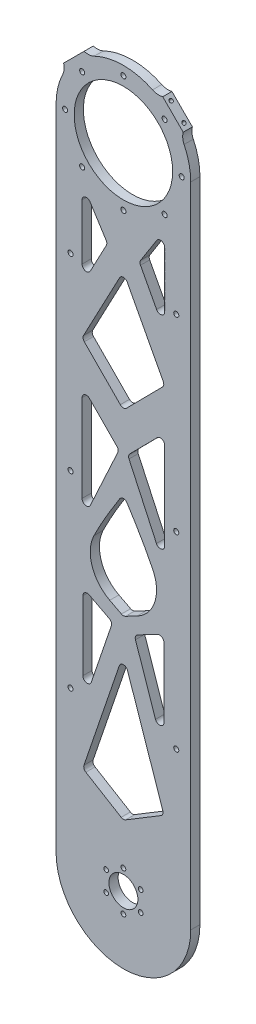
SolidWorks part; units mm, degrees
material "6061-T6 (SS)"
ref_plane "Front Plane" through (0, 0, 0) normal (0, 0, 1) x (1, 0, 0)
ref_plane "Top Plane" through (0, 0, 0) normal (0, 1, 0) x (1, 0, 0)
ref_plane "Right Plane" through (0, 0, 0) normal (1, 0, 0) x (0, 0, -1)
sketch "Sketch2" plane through (0, 0, 0) normal (0, 0, 1) x (1, 0, 0)
  line L0 (0, 0) -> (0, 500) construction
  line L1 (-46.5, 0) -> (-46.5, 500)
  line L2 (46.5, 0) -> (46.5, 500)
  arc A0 (-46.5, 0) -> (46.5, 0) centre (0, 0) ccw
  arc A1 (46.5, 500) -> (-46.5, 500) centre (0, 500) ccw
  circle A2 centre (0, 500) radius 37.25 construction
  circle A3 centre (0, 0) radius 10
  circle A4 centre (0, 13.75) radius 1.65
  circle A5 centre (0, 0) radius 13.75 construction
  circle A6 centre (11.9078, 6.875) radius 1.65
  circle A7 centre (11.9078, -6.875) radius 1.65
  circle A8 centre (0, -13.75) radius 1.65
  circle A9 centre (-11.9078, -6.875) radius 1.65
  circle A10 centre (-11.9078, 6.875) radius 1.65
  point P3 (0, 250)
  point P27 (0, 0)
  dimension "D2" = 74.5
  dimension "D4" = 20
  dimension "D5" = 3.3
  dimension "D6" = 27.5
  dimension "D3" = 46.5
  dimension "D1" = 500
  dimension "D7" = 6
extrude "Boss-Extrude1" add sketch "Sketch2" along normal blind 6.35
sketch "Sketch4" plane through (0, 0, 6.35) normal (0, 0, 1) x (1, 0, 0)
  line L0 (0, 500) -> (0, 999.1647) construction
  line L29 (46.5, 500) -> (-46.5, 500) construction
  line L31 (28.0053, 59.376) -> (0, 42.4117)
  line L32 (0, 141.6934) -> (28.0053, 59.376)
  line L33 (-28.0053, 59.376) -> (0, 141.6934)
  line L34 (0, 42.4117) -> (-28.0053, 59.376)
  line L35 (-7.5, 156.9059) -> (-28.0053, 96.6336)
  line L36 (-28.0053, 167.5829) -> (-7.5, 156.9059)
  line L37 (-28.0053, 96.6336) -> (-28.0053, 167.5829)
  line L38 (28.0053, 167.5829) -> (7.5, 156.9059)
  line L39 (28.0053, 96.6336) -> (28.0053, 167.5829)
  line L40 (7.5, 156.9059) -> (28.0053, 96.6336)
  line L41 (0, 164.2751) -> (28.5505, 179.1412)
  line L42 (0, 164.2751) -> (-28.5505, 179.1412)
  line L43 (28.5505, 259.5868) -> (3, 314.9383)
  line L44 (28.5505, 340.7931) -> (28.5505, 259.5868)
  line L45 (3, 314.9383) -> (28.5505, 340.7931)
  line L46 (-3, 314.9383) -> (-28.5505, 340.7931)
  line L47 (-28.5505, 259.5868) -> (-3, 314.9383)
  line L48 (-28.5505, 340.7931) -> (-28.5505, 259.5868)
  line L49 (0, 423.1428) -> (-28.5505, 369.2462)
  line L50 (-28.5505, 369.2462) -> (0, 340.3557)
  line L51 (0, 340.3557) -> (28.5505, 369.2462)
  line L52 (0, 423.1428) -> (28.5505, 369.2462)
  line L53 (-28.5505, 462.0952) -> (-28.5505, 401.2902)
  line L54 (-11, 434.4215) -> (-28.5505, 462.0952)
  line L55 (-28.5505, 401.2902) -> (-11, 434.4215)
  line L56 (28.5505, 401.2902) -> (11, 434.4215)
  line L57 (28.5505, 462.0952) -> (28.5505, 401.2902)
  line L58 (11, 434.4215) -> (28.5505, 462.0952)
  arc A0 (46.5, 500) -> (-46.5, 500) centre (0, 500) ccw construction
  arc A1 (46.5, 500) -> (-46.5, 500) centre (0, 500) ccw construction
  spline S2 degree 3 poles (28.5505, 179.1412) (45.3203, 216.9857) (19.4301, 259.7903) (0, 290.0258) knots 0 0 0 0 1 1 1 1
  spline S3 degree 3 poles (-28.5505, 179.1412) (-45.3203, 216.9857) (-19.4301, 259.7903) (0, 290.0258) knots 0 0 0 0 1 1 1 1
extrude "Cut-Extrude1" cut sketch "Sketch4" against normal blind 10
fillet "Fillet3" radius 3 30 edges at (-11, 434.4215, 3.175) (-28.5505, 401.2902, 3.175) (28.5505, 401.2902, 3.175) (11, 434.4215, 3.175) (28.5505, 462.0952, 3.175) (-28.5505, 462.0952, 3.175) (0, 423.1428, 3.175) (-28.5505, 369.2462, 3.175) (28.5505, 369.2462, 3.175) (0, 340.3557, 3.175) (28.5505, 340.7931, 3.175) (-28.5505, 340.7931, 3.175) (-3, 314.9383, 3.175) (3, 314.9383, 3.175) (28.5505, 259.5868, 3.175) (-28.5505, 259.5868, 3.175) (28.5505, 179.1412, 3.175) (0, 290.0258, 3.175) (-28.5505, 179.1412, 3.175) (0, 164.2751, 3.175) (-28.0053, 96.6336, 3.175) (28.0053, 96.6336, 3.175) (7.5, 156.9059, 3.175) (-28.0053, 167.5829, 3.175) (28.0053, 167.5829, 3.175) (0, 141.6934, 3.175) (28.0053, 59.376, 3.175) (-28.0053, 59.376, 3.175) (0, 42.4117, 3.175) (-7.5, 156.9059, 3.175)
sketch "Sketch5" plane through (0, 0, 6.35) normal (0, 0, 1) x (1, 0, 0)
  line L0 (0, -46.5) -> (108.8395, -46.5) construction
  line L1 (46.5, 100) -> (-46.5, 100) construction
  line L2 (46.5, 0) -> (46.5, 500) construction
  line L3 (-46.5, 500) -> (-46.5, 0) construction
  line L4 (-46.5, 106.35) -> (46.5, 106.35) construction
  line L5 (36.5, 106.35) -> (36.5, 100) construction
  line L6 (0, 106.35) -> (0, 100) construction
  line L7 (-46.5, 256.35) -> (46.5, 256.35) construction
  line L8 (-46.5, 181.35) -> (46.5, 181.35) construction
  line L9 (-46.5, 337.7) -> (46.5, 337.7) construction
  arc A1 (-46.5, 0) -> (46.5, 0) centre (0, 0) ccw construction
  circle A2 centre (36.5, 103.175) radius 1.75
  circle A3 centre (-36.5, 103.175) radius 1.75
  circle A4 centre (36.5, 259.525) radius 1.75
  circle A5 centre (-36.5, 259.525) radius 1.75
  circle A6 centre (36.5, 415.875) radius 1.75
  circle A7 centre (-36.5, 415.875) radius 1.75
  point P18 (36.5, 103.175)
  dimension "D2" = 3.5
  dimension "D1" = 146.5
  dimension "D3" = 10
  dimension "D4" = 6.35
  dimension "D5" = 150
  dimension "D6" = 81.35
  dimension "D7" = 81.35
extrude "Cut-Extrude2" cut sketch "Sketch5" against normal through all
sketch "Sketch6" plane through (0, 0, 6.35) normal (0, 0, 1) x (1, 0, 0)
  circle A0 centre (0, 500) radius 26.5
  arc A1 (46.5, 500) -> (-46.5, 500) centre (0, 500) ccw construction
  arc A2 (46.5, 500) -> (-46.5, 500) centre (0, 500) ccw construction
  dimension "D1" = 20
extrude "Cut-Extrude3" cut sketch "Sketch6" against normal blind 10
sketch "Sketch7" plane through (0, 0, 6.35) normal (0, 0, 1) x (1, 0, 0)
  line L1 (40.0163, 523.6842) -> (44.1104, 529.9682) construction
  line L2 (23.6842, 540.0163) -> (29.9682, 544.1104) construction
  line L3 (44.1104, 529.9682) -> (29.9682, 544.1104)
  line L4 (0, 500) -> (37.0393, 537.0393) construction
  line L5 (0, 500) -> (0, 546.5) construction
  arc A0 (46.5, 500) -> (-46.5, 500) centre (0, 500) ccw construction
  arc A1 (29.9682, 544.1104) -> (16.4747, 543.4837) centre (22.4977, 559.381) cw
  arc A2 (44.1104, 529.9682) -> (43.4837, 516.4747) centre (59.381, 522.4977) ccw
  arc A3 (16.4747, 543.4837) -> (43.4837, 516.4747) centre (0, 500) cw
  dimension "D3" = 17
  dimension "D5" = 17
  dimension "D1" = 20
  dimension "D2" = 7.5
  dimension "D4" = 8
  dimension "D6" = 8
  dimension "D7" = 45
extrude "Boss-Extrude2" add sketch "Sketch7" against normal up to surface (6.35 mm away) up to face at (26.5, 500, 0)
sketch "Sketch8" plane through (287.0393, 287.0393, 0) normal (0.7071, 0.7071, 0) x (0, 0, -1)
  line L0 (0, 363.5534) -> (-6.35, 363.5534) construction
  line L1 (0, 343.5534) -> (-6.35, 343.5534) construction
  line L2 (-6.35, 343.5534) -> (-6.35, 363.5534) construction
  point P0 (-3.175, 359.5534)
  point P1 (-3.175, 347.5534)
  dimension "D1" = 4
  dimension "D2" = 4
  dimension "D3" = 3.175
hole_wizard "Tap Drill for M3x0.5 Tap1" positions "Sketch8" profile "Sketch9" hole size "M3x0.5" standard "ANSI Metric"
sketch "Sketch9" plane through (32.7967, 541.282, 3.175) normal (0, 0, 1) x (-0.7071, 0.7071, 0)
  line L0 (0, 0) -> (0, 5.7511)
  line L1 (0, 5.7511) -> (1.25, 5)
  line L2 (1.25, 5) -> (1.25, 0)
  line L5 (1.25, 0) -> (0, 0)
  line L10 (0, 5.7511) -> (-1.25, 5) construction
  line L11 (0, -6.35) -> (0, 107.95) construction
  dimension "Hole Dia." = 2.5
  dimension "Hole Depth" = 5
  dimension "Drill Angle" = 118
pattern_circular "CirPattern2" count 2 every 90 about axis through (0, 500, -3.65) along (0, 0, 1) of "Boss-Extrude2", "Tap Drill for M3x0.5 Tap1"
sketch "Sketch10" plane through (0, 0, 6.35) normal (0, 0, 1) x (1, 0, 0)
  line L0 (-43.4837, 516.4747) -> (-63.4837, 516.4747)
  line L1 (43.4837, 516.4747) -> (63.4837, 516.4747)
  arc A0 (43.4837, 516.4747) -> (-43.4837, 516.4747) centre (0, 500) ccw
  arc A1 (46.5, 500) -> (43.4837, 516.4747) centre (0, 500) ccw construction
  arc A2 (-63.4837, 516.4747) -> (63.4837, 516.4747) centre (0, 500) cw
  dimension "D1" = 19.0866
  dimension "D2" = 20
extrude "Cut-Extrude4" cut sketch "Sketch10" against normal through all
sketch "Sketch11" plane through (0, 0, 6.35) normal (0, 0, 1) x (1, 0, 0)
  circle A0 centre (0, 500) radius 34
  circle A1 centre (0, 500) radius 26.5 construction
  dimension "D1" = 68
extrude "Cut-Extrude5" cut sketch "Sketch11" against normal through all
sketch "Sketch12" plane through (0, 0, 6.35) normal (0, 0, 1) x (1, 0, 0)
  line L0 (0, 534) -> (0, 546.5) construction
  circle A0 centre (0, 500) radius 40.25 construction
  circle A1 centre (0, 500) radius 34 construction
  circle A3 centre (0, 540.25) radius 1.75
  circle A4 centre (28.461, 528.461) radius 1.75
  circle A5 centre (40.25, 500) radius 1.75
  circle A6 centre (28.461, 471.539) radius 1.75
  circle A7 centre (0, 459.75) radius 1.75
  circle A8 centre (-28.461, 471.539) radius 1.75
  circle A9 centre (-40.25, 500) radius 1.75
  circle A10 centre (-28.461, 528.461) radius 1.75
  arc A11 (46.5, 500) -> (-46.5, 500) centre (0, 500) ccw construction
  point P4 (0, 540.25)
  point P36 (0, 500)
  dimension "D1" = 3.5
  dimension "D2" = 8
extrude "Cut-Extrude6" cut sketch "Sketch12" against normal through all both and the other way through all
sketch "Sketch13" plane through (0, 0, 0) normal (0, 0, -1) x (-1, 0, 0)
  line L0 (28.984, 180.1429) -> (28.984, 234.0954) construction
  line L1 (-28.984, 180.1429) -> (-28.984, 234.0954) construction
  line L2 (46.5, 234.0954) -> (-46.5, 234.0954)
  line L3 (46.5, 500) -> (46.5, 0) construction
  line L4 (-46.5, 0) -> (-46.5, 500) construction
  line L5 (46.5, 180.1429) -> (-46.5, 180.1429)
  line L6 (-46.5, 234.0954) -> (-46.5, 180.1429)
  line L7 (46.5, 234.0954) -> (46.5, 180.1429)
  spline S0 degree 3 poles (2.5314, 286.068) (21.3968, 256.4039) (44.1773, 216.1126) (28.984, 180.1429) knots 0.042883 0.042883 0.042883 0.042883 0.991187 0.991187 0.991187 0.991187 construction
  spline S1 degree 3 poles (-28.984, 180.1429) (-44.1773, 216.1126) (-21.3968, 256.4039) (-2.5314, 286.068) knots 0.008813 0.008813 0.008813 0.008813 0.957117 0.957117 0.957117 0.957117 construction
extrude "Cut-Extrude7" cut sketch "Sketch13" against normal through all
move or copy body "Body-Move/Copy1" bodies to move or copy 111 copy no translate (0, -52.7177, 0) parameters "D1"=0, "D2"=52.7177, "D3"=0
sketch "Sketch14" plane through (0, 180.1429, 0) normal (0, 1, 0) x (1, 0, 0)
  line L0 (-28.984, 0) -> (-46.5, 0) construction
  line L1 (-46.5, 0) -> (-46.5, -6.35) construction
  line L2 (-46.5, -6.35) -> (-28.984, -6.35) construction
  line L3 (-28.984, -6.35) -> (-28.984, 0) construction
  line L4 (28.984, -6.35) -> (46.5, -6.35) construction
  line L5 (46.5, -6.35) -> (46.5, 0) construction
  line L6 (46.5, 0) -> (28.984, 0) construction
  line L7 (28.984, 0) -> (28.984, -6.35) construction
  line L8 (-28.984, 0) -> (-46.5, 0)
  line L9 (-46.5, 0) -> (-46.5, -6.35)
  line L10 (-46.5, -6.35) -> (-28.984, -6.35)
  line L11 (-28.984, -6.35) -> (-28.984, 0)
  line L12 (28.984, -6.35) -> (46.5, -6.35)
  line L13 (46.5, -6.35) -> (46.5, 0)
  line L14 (46.5, 0) -> (28.984, 0)
  line L15 (28.984, 0) -> (28.984, -6.35)
extrude "Boss-Extrude3" add sketch "Sketch14" along normal up to surface (1.2348 mm away) up to face at (37.742, 181.3777, 3.175)
sketch "Sketch15" plane through (0, 0, 0) normal (0, 0, -1) x (-1, 0, 0)
  line L0 (-1.3855, 164.9966) -> (-27.606, 178.6494) construction
  line L1 (28.984, 181.3777) -> (28.984, 180.1429)
  line L2 (-28.984, 181.3777) -> (-28.984, 180.1429) construction
  line L3 (-9.4381, 169.1895) -> (-27.606, 178.6494)
  line L4 (-28.984, 181.3777) -> (-28.984, 180.1429)
  line L5 (0, 493.7823) -> (0, -46.5) construction
  line L6 (9.4381, 169.1895) -> (27.606, 178.6494)
  arc A0 (-20.3344, 202.3794) -> (-9.4381, 169.1895) centre (2.1078, 191.3636) ccw
  arc A1 (-28.984, 180.1429) -> (-27.606, 178.6494) centre (-26.2204, 181.3103) ccw construction
  arc A2 (-28.984, 180.1429) -> (-27.606, 178.6494) centre (-26.2204, 181.3103) ccw
  arc A3 (46.5, 447.2823) -> (-46.5, 447.2823) centre (0, 447.2823) ccw construction
  arc A4 (-46.5, 0) -> (46.5, 0) centre (0, 0) ccw construction
  arc A5 (28.984, 180.1429) -> (27.606, 178.6494) centre (26.2204, 181.3103) cw
  arc A6 (20.3344, 202.3794) -> (9.4381, 169.1895) centre (-2.1078, 191.3636) cw
  spline S0 degree 3 poles (1953.7087, 263.1445) (-2215.7642, -533.3919) (2154.4506, 1213.369) (-1849.5555, -532.5784) knots -2.670349 -2.670349 -2.670349 -2.670349 4.338748 4.338748 4.338748 4.338748 only from (-28.984, 181.3777) to (-2.5314, 233.3503) construction
  spline S1 degree 3 poles (28.984, 181.3777) (26.6659, 188.5284) (23.6788, 195.566) (20.3344, 202.3794) knots 0.47109 0.47109 0.47109 0.47109 0.656208 0.656208 0.656208 0.656208
  spline S2 degree 3 poles (-28.984, 181.3777) (-26.6659, 188.5284) (-23.6788, 195.566) (-20.3344, 202.3794) knots 0.47109 0.47109 0.47109 0.47109 0.656208 0.656208 0.656208 0.656208
  dimension "D1" = 25
  dimension "D2" = 540.2823
extrude "Boss-Extrude4" add sketch "Sketch15" against normal up to surface (6.35 mm away) up to face at (2.6453, 187.7844, 6.35)
sketch "Sketch16" plane through (0, 0, 0) normal (0, 0, -1) x (-1, 0, 0)
  line L0 (36.5, 103.175) -> (36.5, 363.1573) construction
  line L1 (-36.5, 103.175) -> (-36.5, 363.1573) construction
  circle A0 centre (-36.5, 363.1573) radius 1.75 construction
  circle A1 centre (36.5, 363.1573) radius 1.75 construction
  circle A2 centre (-36.5, 103.175) radius 1.75 construction
  circle A3 centre (36.5, 103.175) radius 1.75 construction
  circle A4 centre (-36.5, 363.1573) radius 1.75 construction
  circle A5 centre (36.5, 363.1573) radius 1.75 construction
  circle A6 centre (-36.5, 103.175) radius 1.75 construction
  circle A7 centre (36.5, 103.175) radius 1.75 construction
  circle A8 centre (36.5, 233.1662) radius 1.75
  circle A9 centre (-36.5, 233.1662) radius 1.75
  point P16 (36.5, 233.1662)
  point P18 (36.5, 233.1662)
extrude "Cut-Extrude8" cut sketch "Sketch16" against normal through all
sketch "Sketch17" plane through (0, 0, 0) normal (0, 0, -1) x (-1, 0, 0)
  circle A0 centre (36.5, 206.8073) radius 1.75 construction
  circle A1 centre (-36.5, 206.8073) radius 1.75 construction
  circle A2 centre (36.5, 206.8073) radius 1.75
  circle A3 centre (-36.5, 206.8073) radius 1.75
extrude "Boss-Extrude5" add sketch "Sketch17" against normal up to surface (6.35 mm away) up to face at (-34.75, 233.1662, 6.35)
sketch "Sketch18" plane through (0, 0, 0) normal (0, 0, -1) x (-1, 0, 0)
  line L0 (0, 447.2823) -> (0, 493.7823) construction
  line L1 (0, 447.2823) -> (32.8805, 480.1628) construction
  line L2 (-10, 492.6943) -> (-10, 495.6943) construction
  line L3 (25.0401, 486.4645) -> (27.1614, 488.5858)
  line L4 (27.1614, 488.5858) -> (41.3035, 474.4437)
  line L5 (41.3035, 474.4437) -> (39.1822, 472.3224)
  line L6 (25.0401, 486.4645) -> (39.1822, 472.3224)
  line L7 (-10, 495.6943) -> (10, 495.6943) construction
  line L8 (10, 495.6943) -> (10, 492.6943) construction
  line L9 (-10, 492.6943) -> (10, 492.6943) construction
  line L10 (-39.1822, 472.3224) -> (-41.3035, 474.4437)
  line L11 (-41.3035, 474.4437) -> (-27.1614, 488.5858)
  line L12 (-27.1614, 488.5858) -> (-25.0401, 486.4645)
  line L13 (-39.1822, 472.3224) -> (-25.0401, 486.4645)
  arc A0 (46.5, 447.2823) -> (-46.5, 447.2823) centre (0, 447.2823) ccw construction
  point P11 (32.1111, 479.3934)
  point P13 (0, 492.6943)
  dimension "D1" = 45
  dimension "D2" = 20
  dimension "D3" = 3
  dimension "D4" = 3
extrude "Boss-Extrude6" add sketch "Sketch18" against normal up to surface (6.35 mm away) up to face at (-34.75, 233.1662, 6.35)
sketch "Sketch20" plane through (-257.8736, 257.8736, 0) normal (-0.7071, 0.7071, 0) x (0, 0, 1)
  line L0 (6.35, 316.2764) -> (0, 316.2764) construction
  line L1 (6.35, 306.2764) -> (6.35, 326.2764) construction
  line L2 (0, 306.2764) -> (0, 326.2764) construction
  point P0 (3.175, 322.5264)
  point P9 (3.175, 316.2764)
  point P10 (3.175, 310.0264)
  dimension "D1" = 12.5
hole_wizard "M3x0.5 Tapped Hole1" positions "Sketch20" profile "Sketch21" tap size "M3x0.5" standard "ANSI Metric"
sketch "Sketch21" plane through (-29.813, 485.9342, 3.175) normal (0, 0, 1) x (-0.7071, -0.7071, 0)
  line L0 (0, 0) -> (0, 8.2511)
  line L1 (0, 8.2511) -> (1.25, 7.5)
  line L2 (1.25, 7.5) -> (1.25, 0)
  line L5 (1.25, 0) -> (0, 0)
  line L10 (0, 8.2511) -> (-1.25, 7.5) construction
  line L11 (0, -6.35) -> (0, 107.95) construction
  dimension "Tap Drill Dia." = 2.5
  dimension "Tap Drill Depth" = 7.5
  dimension "Drill Angle" = 118
cosmetic thread "Hole Thread1" parameters "D1"=6, "D2"=3
cosmetic thread "Hole Thread2" parameters "D1"=6, "D2"=3
pattern_circular "CirPattern3" count 2 over 90 about axis through (0, 447.2823, 0) along (0, 0, 1) of "M3x0.5 Tapped Hole1" reverse direction yes
cosmetic thread "Hole Thread5" parameters "D1"=6, "D2"=3
cosmetic thread "Hole Thread6" parameters "D1"=6, "D2"=3
cosmetic thread "Hole Thread7" parameters "D1"=6, "D2"=3
cosmetic thread "Hole Thread8" parameters "D1"=6, "D2"=3
fillet "Fillet4" radius 10 4 edges at (-39.1822, 472.3224, 3.175) (-25.0401, 486.4645, 3.175) (39.1822, 472.3224, 3.175) (25.0401, 486.4645, 3.175)
equation "\"L1L\"=500"
equation "\"L1Thick\"=6.35"
equation "\"D1@Sketch2\"=\"L1L\""
equation "\"Harm-Drive-Outer\"=74.5"
equation "\"D2@Sketch2\"=\"Harm-Drive-Outer\""
equation "\"D1@Boss-Extrude1\"=\"L1Thick\""
